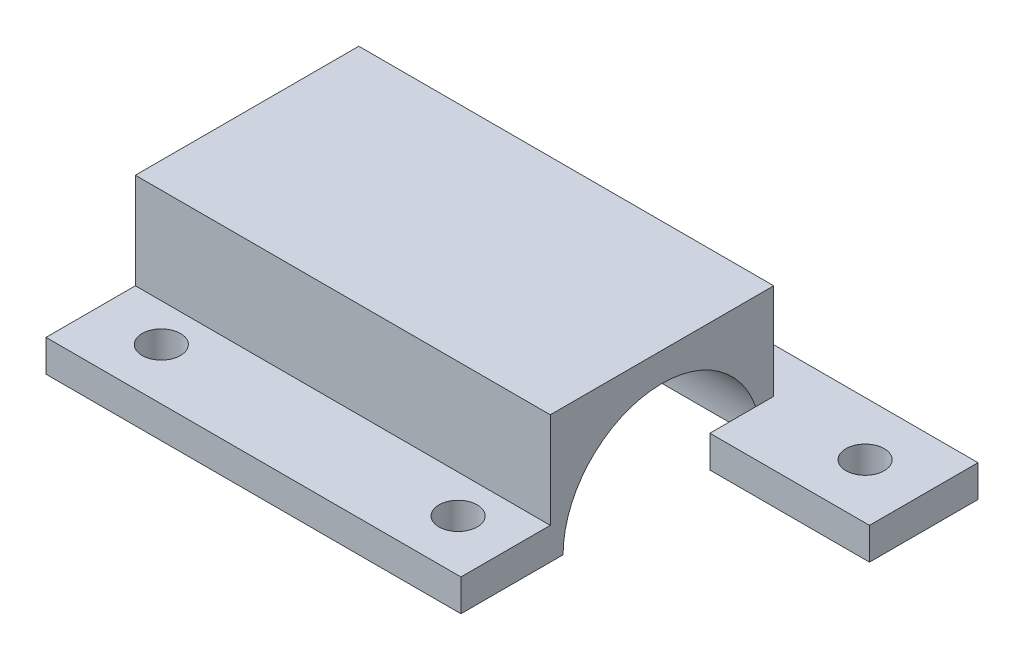
SolidWorks part; units mm, degrees
ref_plane "前视基准面" through (0, 0, 0) normal (0, 0, 1) x (1, 0, 0)
ref_plane "上视基准面" through (0, 0, 0) normal (0, 1, 0) x (1, 0, 0)
ref_plane "右视基准面" through (0, 0, 0) normal (1, 0, 0) x (0, 0, -1)
other "Configuration Table"
sketch "草图1" plane through (0, 0, 0) normal (1, 0, 0) x (0, 0, -1)
  line L0 (-6.3, 0) -> (6.3, 0)
  line L9 (-6.3, 0) -> (-6.3, 4)
  line L14 (-6.3, 4) -> (6.3, 4)
  line L15 (6.3, 4) -> (6.3, 0)
  line L16 (-3.5, 4) -> (-3.5, 0)
  line L17 (3.5, 4) -> (3.5, 0)
  line L18 (-6.3, 1) -> (-3.5, 1)
  line L19 (3.5, 1) -> (6.3, 1)
  line L20 (4.9, 1) -> (4.9, 0)
  circle A0 centre (0, 0) radius 3.1
  circle A2 centre (0, 0) radius 1.5
  dimension "D1" = 6.2
  dimension "D2" = 2.8
  dimension "D7" = 3
  dimension "D3" = 4
  dimension "D4" = 3.5
  dimension "D5" = 3.5
  dimension "D6" = 1
  dimension "D8" = 1.4
extrude "凸台-拉伸1" add sketch "草图1" against normal blind 18 contours L9 L16 L18 | L17 L15 L19 | A0 L17 L14 L16 region at (0, 0.5, 4.9) region at (0, 0.5, 3.4194) region at (0, 0.5, -4.2)
sketch "草图2" plane through (0, 1, 0) normal (0, 1, 0) x (1, 0, 0)
  circle A2 centre (-16, -4.6875) radius 0.6
  circle A3 centre (-6.7, -4.6875) radius 0.6
  dimension "D1" = 1.2
extrude "切除-拉伸1" cut sketch "草图2" against normal through all contours A2 | A3
sketch "草图3" plane through (0, 0, 0) normal (1, 0, 0) x (0, 0, -1)
  line L1 (-3.5, 4) -> (3.5, 4)
  line L2 (-3.5, 4) -> (-3.5, 1)
  line L3 (-3.5, 1) -> (3.5, 1)
  line L4 (3.5, 4) -> (3.5, 1)
extrude "切除-拉伸2" cut sketch "草图3" against normal blind 5
sketch "草图4" plane through (0, 1, 0) normal (0, 1, 0) x (1, 0, 0)
  line L0 (-5, 3.5) -> (-5, -3.5) construction
  line L1 (0, 4.9) -> (-5, 4.9)
  line L2 (0, 4.9) -> (0, 1.5)
  line L3 (0, 1.5) -> (-5, 1.5)
  line L4 (-5, 4.9) -> (-5, 1.5)
  dimension "D1" = 3.4
extrude "凸台-拉伸2" add sketch "草图4" against normal up to surface (1 mm away) up to face at (-9, 0, -4)
sketch "草图5" plane through (0, 1, 0) normal (0, 1, 0) x (1, 0, 0)
  circle A0 centre (-1.85, 3.2125) radius 0.6
  dimension "D1" = 1.2
extrude "切除-拉伸3" cut sketch "草图5" against normal through all
sketch "草图7" plane through (0, 0, 0) normal (1, 0, 0) x (0, 0, -1)
  line L1 (-2.9343, 1) -> (-6.3, 1)
  line L2 (-2.9343, 1) -> (-2.9343, 0)
  line L3 (-2.9343, 0) -> (-6.3, 0)
  line L4 (-6.3, 1) -> (-6.3, 0)
extrude "切除-拉伸4" cut sketch "草图7" against normal up to surface (5 mm away) up to face at (-5, 2.35, 0)
